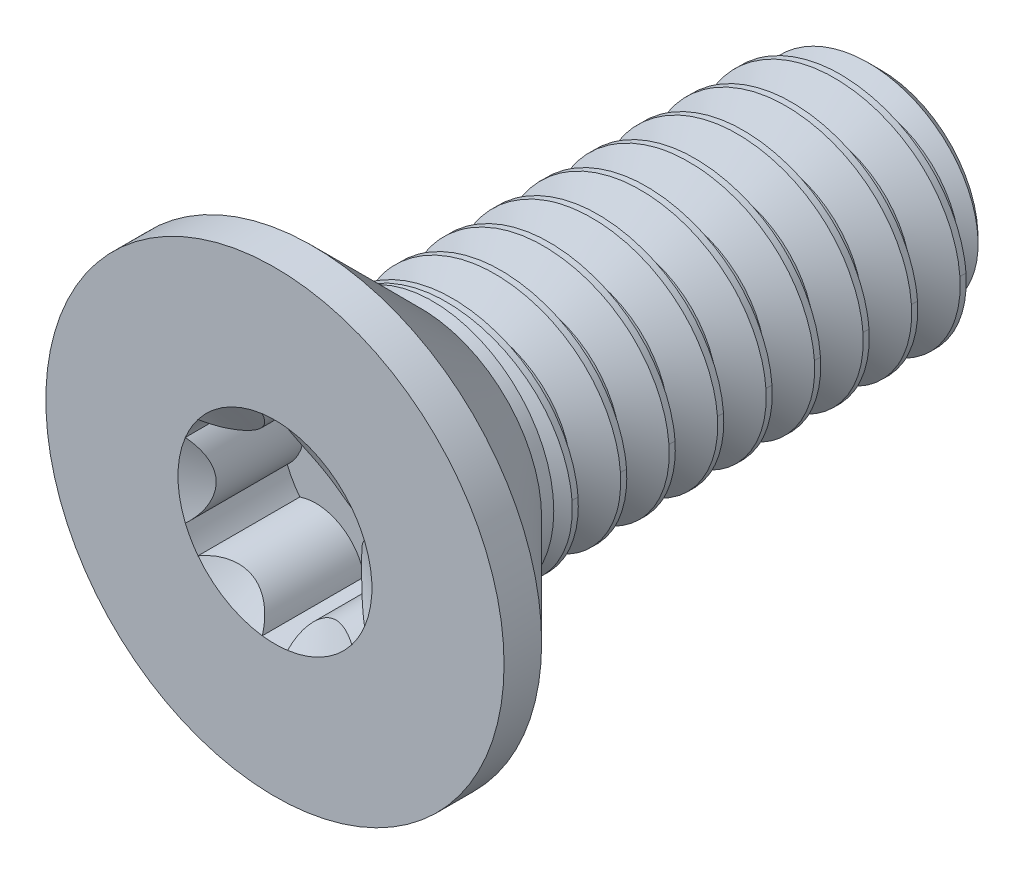
SolidWorks part; units mm, degrees
ref_plane "Front" through (0, 0, 0) normal (0, 0, 1) x (1, 0, 0)
ref_plane "Top" through (0, 0, 0) normal (0, 1, 0) x (1, 0, 0)
ref_plane "Right" through (0, 0, 0) normal (1, 0, 0) x (0, 0, -1)
sketch "Sketch1" plane through (0, 0, 0) normal (1, 0, 0) x (0, 0, -1)
  line L0 (0, 1.89) -> (1.2, 1.89) construction
  line L2 (0, 0) -> (5, 0) construction
  line L4 (5, 1) -> (1.2, 1) construction
  line L5 (0, 0) -> (0, 1.89) construction
  line L6 (0, 1.89) -> (0, -1.89) construction
  line L7 (5, 1) -> (5, -1) construction
  line L8 (0, -1.89) -> (1.2, -1.89) construction
  line L9 (0.31, 1.89) -> (2.2, 0) construction
  line L11 (5, -1) -> (1.2, -1) construction
  line L13 (0.31, 1.89) -> (0.31, -1.89) construction
  line L14 (0.31, -1.89) -> (2.2, 0) construction
  line L15 (1.2, 1.89) -> (1.2, 1) construction
  line L16 (5, 1) -> (5.4, 1) construction
  point P5 (0.31, 1.89)
  point P17 (4, -1)
  dimension "Head Angle" = 90
  dimension "D1" = 1
sketch "Sketch12" plane through (0, 0, 0) normal (1, 0, 0) x (0, 0, -1)
  line L0 (0, 0) -> (5, 0)
  line L1 (5, 0) -> (5, 1)
  line L2 (5, 1) -> (1.2, 1)
  line L3 (1.2, 1) -> (0.31, 1.89)
  line L4 (0.31, 1.89) -> (0, 1.89)
  line L5 (0, 1.89) -> (0, 0)
revolve "Revolve3" add sketch "Sketch12" angle 360 about L0
chamfer "Chamfer1" distance 0.2 angle 45 1 edges at (1, 0, -5)
sketch "Sketch5" plane through (0, 0, 0) normal (0, 0, 1) x (1, 0, 0)
  line L0 (0, 0) -> (-0.8, 0) construction
  line L1 (0, 0) -> (-0.6928, 0.4) construction
  line L2 (0, 0) -> (-0.6928, -0.4) construction
  line L3 (-0.6928, -0.4) -> (0, 0)
  line L4 (0, 0) -> (-0.6928, 0.4)
  line L5 (0, 0) -> (-0.7391, -0.3061) construction
  line L6 (0, 0.8) -> (0, 0.7) construction
  line L7 (0, 0.7) -> (0, 0.6) construction
  circle A0 centre (0, 0) radius 0.8 construction
  circle A1 centre (0, 0) radius 0.7 construction
  circle A2 centre (0, 0) radius 0.6 construction
  arc A4 (-0.7391, -0.3061) -> (-0.7391, 0.3061) centre (-1.0064, 0) ccw
  arc A5 (-0.7391, 0.3061) -> (-0.6928, 0.4) centre (0, 0) cw
  arc A6 (-0.7391, -0.3061) -> (-0.6928, -0.4) centre (0, 0) ccw
  point P13 (0, -0.6)
  dimension "D3" = 1.2
  dimension "D4" = 30
  dimension "D5" = 30
  dimension "D1" = 7.5
extrude "Cut-Extrude2" cut sketch "Sketch5" against normal blind 0.84
pattern_circular "CirPattern1" count 6 over 360 about axis through (0, 0, 0) along (0, 0, -1) of "Cut-Extrude2"
sketch "Sketch6" plane through (0, 0, 0) normal (0, 0, 1) x (1, 0, 0)
  circle A0 centre (0, 0) radius 0.8
extrude "Cut-Extrude3" cut sketch "Sketch6" against normal blind 0.84 draft 60
ref_plane "Plane1" through (0, 0, -1.2) normal (0, 0, 1) x (1, 0, 0)
split "Split1" trim tools "Plane1" bodies to split 113 resulting bodies 132 133
sketch "Sketch13" plane through (0, 0, -5) normal (0, 0, -1) x (-1, 0, 0)
  circle A0 centre (0, 0) radius 1
curve "Helix/Spiral1" pitch 0.4 height 4.18 radius 1 centre (0, 0, -5) axis (0, 0, 1) start towards (0, 1, 0)
sketch "Sketch14" plane through (0, 0, 0) normal (1, 0, 0) x (0, 0, -1)
  line L0 (4.975, 1.0433) -> (5.375, 1.0433) construction
  line L1 (5.375, 1.0433) -> (5.175, 0.6969) construction
  line L2 (5.175, 0.6969) -> (4.975, 1.0433) construction
  line L3 (5.175, 0.6969) -> (5.175, 0.7402) construction
  line L4 (5.175, 0.7402) -> (5.175, 1) construction
  line L5 (5.175, 1) -> (5.175, 1.0433) construction
  line L6 (5, 1) -> (5.35, 1) construction
  line L8 (4.9875, 1.0217) -> (5.3625, 1.0217) construction
  line L9 (5.15, 0.7402) -> (5.2, 0.7402)
  line L10 (5.15, 0.7402) -> (5.2, 0.7402) construction
  line L11 (5.2, 0.7402) -> (5.3625, 1.0217)
  line L12 (5.3625, 1.0217) -> (4.9875, 1.0217)
  line L13 (4.9875, 1.0217) -> (5.15, 0.7402)
  point P8 (5.175, 1)
  point P13 (5.175, 0.7402)
  point P15 (5.175, 1.0217)
  point P16 (5.175, 1.0217)
  dimension "D1" = 0.4
  dimension "D2" = 0.05
sweep "Cut-Sweep2" cut profiles "Sketch14" path "Helix/Spiral1" align with end faces yes
sketch "Sketch15" plane through (0, 0, 0) normal (1, 0, 0) x (0, 0, -1)
  line L0 (1.2, 1) -> (1.3, 1)
  line L1 (5, 1) -> (1.2, 1) construction
  line L2 (1.3, 1) -> (1.8774, 0)
  line L3 (0, 0) -> (5, 0) construction
  line L6 (1.2, 1) -> (1.2, 0)
  line L7 (1.2, -1) -> (1.2, 1) construction
  line L8 (1.2, 0) -> (1.8774, 0)
  dimension "D2" = 0.1
  dimension "D1" = 60
revolve "Revolve4" add sketch "Sketch15" angle 360 about L2
ref_axis "Center Axis 1" through (0, 0, -0.2102) along (0, 0, -1)
ref_plane "Contact Plane 1" through (0, 0, -5) normal (0, 0, -1) x (-1, 0, 0)
ref_plane "Contact Plane 2" through (0, 0, 0) normal (0, 0, 1) x (1, 0, 0)
equation "\"D1@Cut-Extrude2\" = \"Head Ht@Sketch1\" * .7"
equation "\"D1@Cut-Extrude3\" = \"D1@Cut-Extrude2\""
equation "\"Torx Dia@Sketch5\" = \"Dia@Sketch1\" * .8"
equation "\"D3@Sketch5\" = \"Torx Dia@Sketch5\" * .75"
equation "\"D1@Chamfer1\"=\"Pitch@Sketch1\"*.5"
equation "\"D3@Helix/Spiral1\"=(\"Lg@Sketch1\"-\"Head Ht@Sketch1\")*1.1"
equation "\"D4@Helix/Spiral1\"=\"Pitch@Sketch1\""
equation "\"D1@Sketch14\"=\"pITCH@sKETCH1\""
equation "\"D2@Sketch14\"=\"D1@Sketch14\"/8"
equation "\"D2@Sketch15\"=\"Pitch@Sketch1\"*.25"
equation "\"D1@Sketch1\"=\"Pitch@Sketch1\"*2.5"
